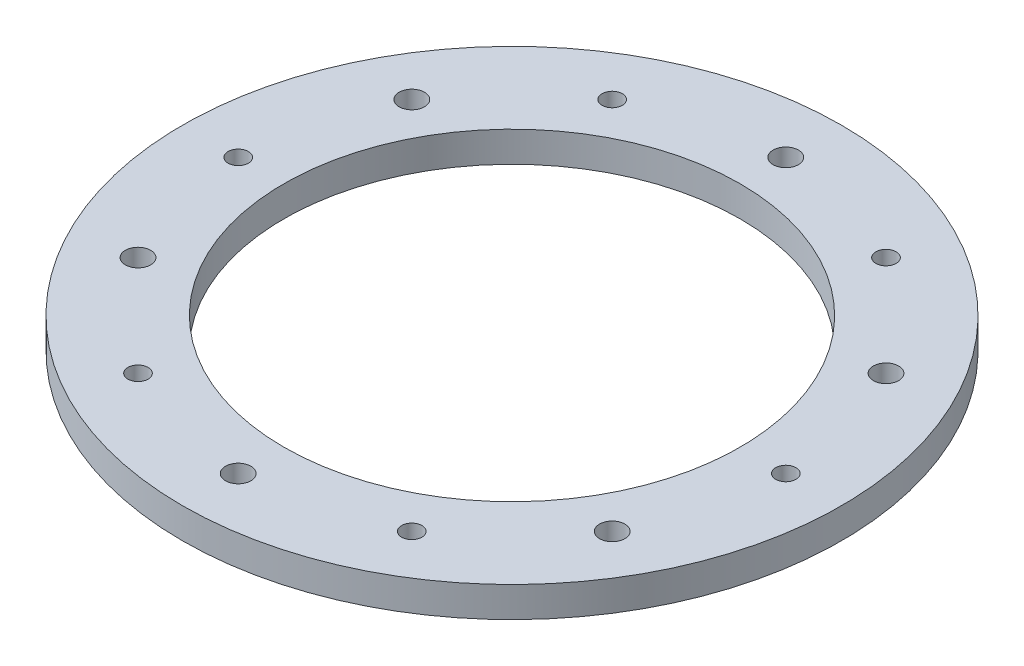
SolidWorks part; units mm, degrees
ref_plane "Front Plane" through (0, 0, 0) normal (0, 0, 1) x (1, 0, 0)
ref_plane "Top Plane" through (0, 0, 0) normal (0, 1, 0) x (1, 0, 0)
ref_plane "Right Plane" through (0, 0, 0) normal (1, 0, 0) x (0, 0, -1)
sketch "Sketch1" plane through (0, 0, 0) normal (0, 1, 0) x (1, 0, 0)
  circle A0 centre (0, 0) radius 32.5
  circle A1 centre (0, 0) radius 27 construction
  circle A2 centre (0, 27) radius 1.25
  circle A3 centre (23.3827, 13.5) radius 1.25
  circle A4 centre (23.3827, -13.5) radius 1.25
  circle A5 centre (0, -27) radius 1.25
  circle A6 centre (-23.3827, -13.5) radius 1.25
  circle A7 centre (-23.3827, 13.5) radius 1.25
  point P18 (0, 0)
  dimension "D1" = 65
  dimension "D2" = 54
  dimension "D3" = 2.5
  dimension "D4" = 6
extrude "Boss-Extrude1" add sketch "Sketch1" along normal blind 3
sketch "Sketch2" plane through (0, 3, 0) normal (0, 1, 0) x (1, 0, 0)
  line L0 (-13.5, 23.3827) -> (0, 0) construction
  line L1 (0, 0) -> (24.248, 0) construction
  circle A0 centre (0, 0) radius 22.5
  circle A1 centre (0, 0) radius 27 construction
  circle A2 centre (-13.5, 23.3827) radius 1
  circle A3 centre (13.5, 23.3827) radius 1
  circle A4 centre (27, 0) radius 1
  circle A5 centre (13.5, -23.3827) radius 1
  circle A6 centre (-13.5, -23.3827) radius 1
  circle A7 centre (-27, 0) radius 1
  point P19 (0, 0)
  dimension "D1" = 45
  dimension "D2" = 54
  dimension "D3" = 2
  dimension "D4" = 120
  dimension "D5" = 6
extrude "Cut-Extrude1" cut sketch "Sketch2" against normal blind 3
